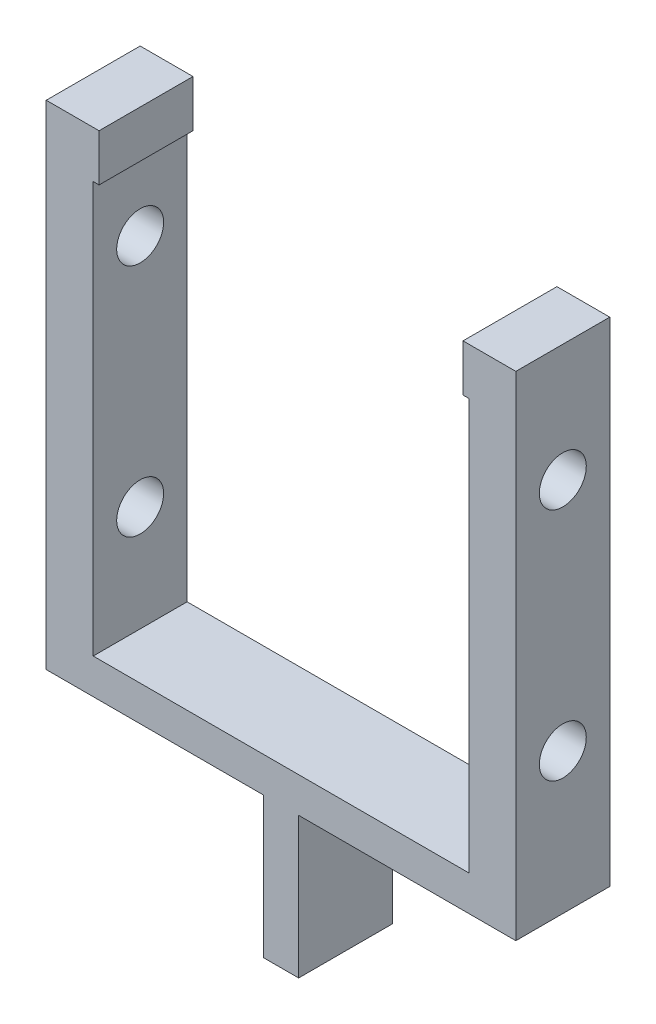
SolidWorks part; units mm, degrees
material "6061 Alloy"
ref_plane "Front Plane" through (0, 0, 0) normal (0, 0, 1) x (1, 0, 0)
ref_plane "Top Plane" through (0, 0, 0) normal (0, 1, 0) x (1, 0, 0)
ref_plane "Right Plane" through (0, 0, 0) normal (1, 0, 0) x (0, 0, -1)
sketch "Sketch1" plane through (0, 0, 0) normal (0, 0, 1) x (1, 0, 0)
  line L7 (4.7625, 0) -> (-4.7625, 0)
  line L13 (-4.7625, 0) -> (-4.7625, 38.1)
  line L14 (-4.7625, 38.1) -> (-63.5, 38.1)
  line L15 (-63.5, 38.1) -> (-63.5, 171.45)
  line L17 (-50.8, 158.75) -> (-50.8, 47.625)
  line L18 (-50.8, 47.625) -> (50.8, 47.625)
  line L19 (0, 47.625) -> (0, 0) construction
  line L20 (50.8, 158.75) -> (50.8, 47.625)
  line L22 (63.5, 38.1) -> (63.5, 171.45)
  line L23 (4.7625, 38.1) -> (63.5, 38.1)
  line L24 (4.7625, 0) -> (4.7625, 38.1)
  line L26 (63.5, 171.45) -> (49.2125, 171.45)
  line L29 (50.8, 158.75) -> (49.2125, 158.75)
  line L30 (49.2125, 171.45) -> (49.2125, 158.75)
  line L31 (-49.2125, 158.75) -> (-49.2125, 171.45)
  line L32 (-49.2125, 158.75) -> (-50.8, 158.75)
  line L33 (49.2125, 158.75) -> (-49.2125, 158.75) construction
  line L34 (-49.2125, 171.45) -> (-63.5, 171.45)
  line L35 (49.2125, 171.45) -> (-49.2125, 171.45) construction
  line L36 (0, -55) -> (0, 55) construction
  line L37 (50.8, 158.75) -> (63.5, 158.75) construction
  point P12 (0, 47.625)
  point P17 (0, 0)
  point P24 (0, 171.45)
  dimension "D1" = 9.525
  dimension "D2" = 101.6
  dimension "D3" = 38.1
  dimension "D5" = 9.525
  dimension "D8" = 133.35
  dimension "D7" = 98.425
  dimension "D4" = 12.7
extrude "Boss-Extrude1" add sketch "Sketch1" along normal mid plane 25.4
sketch "Sketch2" plane through (-63.5, 0, 0) normal (-1, 0, 0) x (0, 0, 1)
  line L0 (-26.0251, 0) -> (40.3307, 0) construction
  line L1 (0, 127) -> (0, 0) construction
  circle A0 centre (0, 76.2) radius 6.35
  circle A1 centre (0, 139.7) radius 6.35
  dimension "D2" = 12.7
  dimension "D1" = 12.7
  dimension "D4" = 63.5
  dimension "D3" = 76.2
extrude "Cut-Extrude1" cut sketch "Sketch2" against normal through all
equation "\"BoomDistance\"=2.5"
equation "\"D4@Sketch2\"= \"BoomDistance\""
equation "\"D7@Sketch1\"=\"D2@Sketch1\"-.125"
equation "\"yokewidth\"=4"
equation "\"D2@Sketch1\"= \"yokewidth\""
equation "\"Pillow_Block_Width\"= 1"
equation "\"D1@Boss-Extrude1\"=\"Pillow_Block_Width\""
